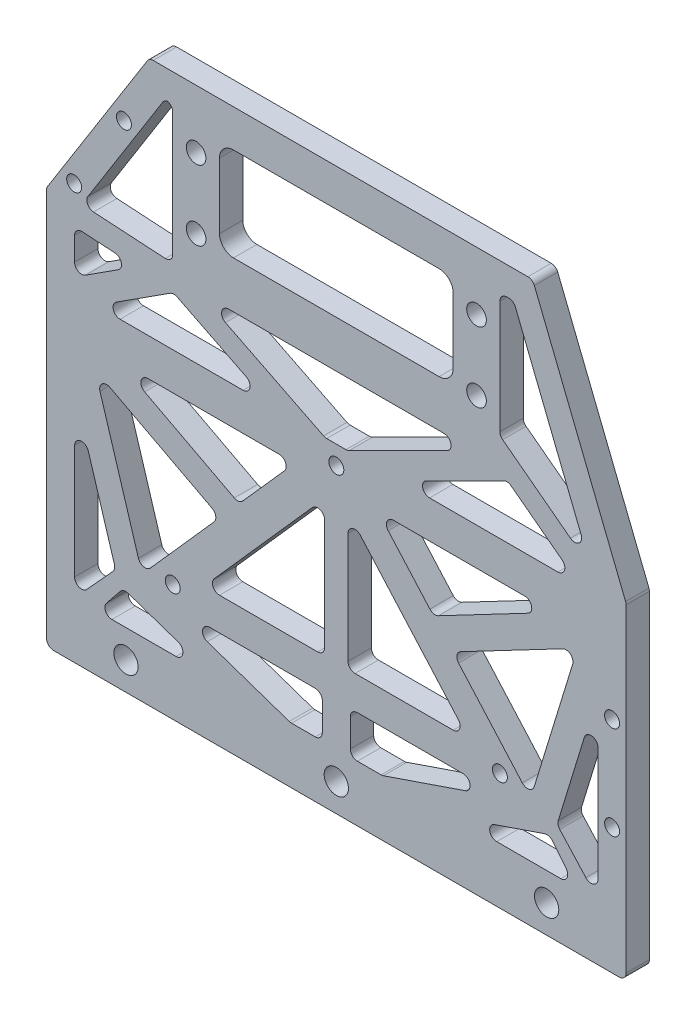
SolidWorks part; units mm, degrees
material "Thornel Mat VMA"
ref_plane "前视基准面" through (0, 0, 0) normal (0, 0, 1) x (1, 0, 0)
ref_plane "上视基准面" through (0, 0, 0) normal (0, 1, 0) x (1, 0, 0)
ref_plane "右视基准面" through (0, 0, 0) normal (1, 0, 0) x (0, 0, -1)
sketch "草图1" plane through (0, 0, 0) normal (0, 0, 1) x (1, 0, 0)
  line L1 (-62, 60) -> (62, 60)
  line L2 (-62, 60) -> (-62, -60)
  line L3 (-62, -60) -> (62, -60)
  line L4 (62, 60) -> (62, -60)
  line L5 (-62, 60) -> (62, -60) construction
  line L6 (-62, -60) -> (62, 60) construction
  point P0 (0, 0)
  dimension "D1" = 124
  dimension "D2" = 120
extrude "凸台-拉伸1" add sketch "草图1" along normal blind 5
sketch "草图2" plane through (0, 0, 5) normal (0, 0, 1) x (1, 0, 0)
  line L0 (-35, -35) -> (35, -35) construction
  line L1 (-62, -60) -> (62, -60) construction
  circle A0 centre (-35, -35) radius 1.6
  circle A1 centre (35, -35) radius 1.6
  point P2 (0, -35)
  dimension "D3" = 3.2
  dimension "D1" = 70
  dimension "D2" = 25
extrude "切除-拉伸1" cut sketch "草图2" against normal through all
sketch "草图3" plane through (0, 0, 5) normal (0, 0, 1) x (1, 0, 0)
  circle A0 centre (0, 4.5) radius 1.6
  circle A1 centre (35, -35) radius 1.6 construction
  dimension "D1" = 3.2
  dimension "D2" = 39.5
extrude "切除-拉伸2" cut sketch "草图3" against normal through all
sketch "草图4" plane through (0, 0, 5) normal (0, 0, 1) x (1, 0, 0)
  line L1 (-30, 47.5) -> (30, 47.5) construction
  line L2 (-30, 47.5) -> (-30, 32.5) construction
  line L3 (-30, 32.5) -> (30, 32.5) construction
  line L4 (30, 47.5) -> (30, 32.5) construction
  line L5 (-30, 47.5) -> (30, 32.5) construction
  line L6 (-30, 32.5) -> (30, 47.5) construction
  circle A0 centre (-30, 47.5) radius 2.1
  circle A1 centre (30, 32.5) radius 2.1
  circle A2 centre (30, 47.5) radius 2.1
  circle A3 centre (-30, 32.5) radius 2.1
  point P0 (0, 40)
  dimension "D4" = 4.2
  dimension "D1" = 40
  dimension "D2" = 15
  dimension "D3" = 60
extrude "切除-拉伸3" cut sketch "草图4" against normal through all
chamfer "倒角1" distance 22 distance2 35 1 edges at (-62, 60, 2.5) first distance on face at (0, 60, 2.5)
chamfer "倒角2" distance 50 distance2 20 1 edges at (62, 60, 2.5) first distance on face at (62, 0, 2.5)
sketch "草图7" plane through (0, 0, 5) normal (0, 0, 1) x (1, 0, 0)
  line L0 (-45, -54) -> (45, -54) construction
  line L1 (-62, -60) -> (62, -60) construction
  circle A0 centre (-45, -54) radius 2.6
  circle A1 centre (0, -54) radius 2.6
  circle A2 centre (45, -54) radius 2.6
  point P4 (0, -54)
  dimension "D3" = 5.2
  dimension "D1" = 6
  dimension "D2" = 90
extrude "切除-拉伸4" cut sketch "草图7" against normal through all
sketch "草图8" plane through (0, 0, 0) normal (0, 0, -1) x (-1, 0, 0)
  circle A0 centre (-59, -33) radius 1.6
  circle A1 centre (-59, -13) radius 1.6
  circle A2 centre (45.4427, 45.7039) radius 1.6
  circle A3 centre (56.0861, 28.7712) radius 1.6
  circle A4 centre (30, 47.5) radius 2.1 construction
  dimension "D1" = 3.2
  dimension "D2" = 45.4427
  dimension "D3" = 56.0861
  dimension "D4" = 59
  dimension "D5" = 28.7712
  dimension "D6" = 45.7039
  dimension "D7" = 13
  dimension "D8" = 33
extrude "切除-拉伸5" cut sketch "草图8" against normal through all
sketch "草图9" plane through (0, 0, 5) normal (0, 0, 1) x (1, 0, 0)
  line L6 (0, 4.5) -> (-35, -35)
  line L7 (25, 52) -> (-25, 52)
  line L8 (25, 52) -> (25, 32)
  line L9 (25, 32) -> (-25, 32)
  line L10 (-25, 52) -> (-25, 32)
  line L11 (25, 52) -> (-25, 32) construction
  line L12 (56, -54) -> (56, 8.8445)
  line L13 (56, 8.8445) -> (37.9378, 54)
  line L14 (37.9378, 54) -> (-36.6846, 54)
  line L15 (-36.6846, 54) -> (-56, 23.2709)
  line L16 (-56, 23.2709) -> (-56, -54)
  line L17 (-56, -54) -> (56, -54)
  line L18 (56, -54) -> (56, 8.8445)
  line L19 (56, 8.8445) -> (37.9378, 54)
  line L20 (37.9378, 54) -> (-36.6846, 54)
  line L21 (-36.6846, 54) -> (-56, 23.2709)
  line L22 (-56, 23.2709) -> (-56, -54)
  line L23 (-56, -54) -> (56, -54)
  line L24 (25, 32) -> (-25, 52) construction
  line L25 (-35, -35) -> (35, -35)
  line L26 (35, -35) -> (0, 4.5)
  line L27 (43.8887, -39) -> (1.8, 8.5)
  line L28 (-1.8, 8.5) -> (-43.8887, -39)
  line L29 (-43.8887, -39) -> (43.8887, -39)
  line L30 (28.3335, -32) -> (0, -0.0236)
  line L31 (0, -0.0236) -> (-28.3335, -32)
  line L32 (-28.3335, -32) -> (28.3335, -32)
  line L33 (56, 4.5) -> (-56, 4.5)
  line L34 (56, 8.5) -> (-56, 8.5)
  line L35 (56, 0.5) -> (-56, 0.5)
  line L36 (43.8887, -39) -> (56, 0.5)
  line L37 (43.8887, -39) -> (56, -54)
  line L38 (-56, 0.5) -> (-43.8887, -39)
  line L39 (-56, -54) -> (-43.8887, -39)
  line L40 (-58.8682, -0.3794) -> (-47.2241, -38.3555)
  line L41 (47.2241, -38.3555) -> (56, -48)
  line L42 (-47.2241, -38.3555) -> (-56, -48)
  line L43 (47.2241, -38.3555) -> (58.8682, -0.3794)
  line L44 (-53.1318, 1.3794) -> (-40.5532, -39.6445)
  line L45 (36.118, 19.7639) -> (39.1448, 21.2773)
  line L46 (-52.8621, 0.5) -> (-22.8444, -15.25)
  line L47 (40.5532, -39.6445) -> (53.1318, 1.3794)
  line L48 (35, 22) -> (-35, 22)
  line L49 (-35, 62) -> (-35, 22)
  line L50 (35, 62) -> (-35, 62)
  line L51 (35, 62) -> (35, 22)
  line L52 (25, 32) -> (56, 8.5)
  line L53 (-35, 22) -> (-56, 23.2709)
  line L54 (-35, 22) -> (-56, 8.5)
  line L55 (-27.2138, 24.0334) -> (-54.6481, 6.3971)
  line L56 (-27.2138, 24.0334) -> (-55.849, 25.7663)
  line L57 (-42.7862, 19.9666) -> (-57.3519, 10.6029)
  line L58 (-42.7862, 19.9666) -> (-56.151, 20.7755)
  line L59 (35, 22) -> (0, 4.5)
  line L60 (-35, 22) -> (0, 4.5)
  line L61 (23.4897, 30.0077) -> (54.4897, 6.5077)
  line L62 (33.882, 24.2361) -> (0, 7.2951)
  line L63 (-33.882, 24.2361) -> (0, 7.2951)
  line L64 (26.5103, 33.9923) -> (57.5103, 10.4923)
  line L65 (36.118, 19.7639) -> (0, 1.7049)
  line L66 (-36.118, 19.7639) -> (0, 1.7049)
  line L67 (0, -0.0236) -> (0, -32)
  line L68 (-2.5, -0.0236) -> (-2.5, -32)
  line L69 (2.5, -0.0236) -> (2.5, -32)
  line L70 (43.8887, -39) -> (0, -54)
  line L71 (0, -54) -> (-43.8887, -39)
  line L72 (43.0801, -36.6344) -> (0, -51.358)
  line L73 (0, -51.358) -> (-43.0801, -36.6344)
  line L74 (52.8621, 0.5) -> (22.8444, -15.25)
  line L75 (51.4683, 3.1565) -> (21.4505, -12.5935)
  line L76 (-56, -48) -> (56, -48)
  line L77 (-54.256, -2.1565) -> (-24.2382, -17.9065)
  line L78 (54.256, -2.1565) -> (24.2382, -17.9065)
  line L79 (-53.6659, -55.8846) -> (-40.5532, -39.6445) construction
  line L80 (40.5532, -39.6445) -> (53.6659, -55.8846) construction
  line L81 (-51.4683, 3.1565) -> (-21.4505, -12.5935)
  line L82 (21.4505, -12.5935) -> (20.7951, -12.9373)
  line L83 (-21.4505, -12.5935) -> (-20.7951, -12.9373)
  line L84 (43.8887, -39) -> (0, 10.5315) construction
  line L85 (0, 10.5315) -> (-43.8887, -39) construction
  line L86 (44.6972, -41.3656) -> (0, -56.642)
  line L87 (0, -56.642) -> (-44.6972, -41.3656)
  line L88 (-44.6972, -41.3656) -> (-45.5605, -41.0706)
  line L89 (44.6972, -41.3656) -> (45.5605, -41.0706)
  line L90 (0, -48) -> (0, -39)
  line L91 (3, -48) -> (3, -39)
  line L92 (-3, -48) -> (-3, -39)
  line L99 (-58.3341, -52.1154) -> (-47.2241, -38.3555) construction
  line L100 (47.2241, -38.3555) -> (58.3341, -52.1154) construction
  point P0 (0, 42)
  dimension "D2" = 42
  dimension "D3" = 20
  dimension "D4" = 50
  dimension "D1" = 6
  dimension "D5" = 4
  dimension "D6" = 3
  dimension "D7" = 4
  dimension "D8" = 4
  dimension "D9" = 3
  dimension "D10" = 3
  dimension "D11" = 10
  dimension "D12" = 2.5
  dimension "D13" = 2.5
  dimension "D14" = 2.5
  dimension "D15" = 2.5
  dimension "D16" = 2.5
  dimension "D17" = 2.5
  dimension "D18" = 2.5
  dimension "D19" = 3
  dimension "D20" = 6
  dimension "D21" = 3
  dimension "D22" = 2.5
  dimension "D23" = 3
  dimension "D24" = 3
extrude "切除-拉伸6" cut sketch "草图9" against normal blind 10 contours L51 L64 L19 L20 | L7 L10 L9 L8 | L56 L49 L20 L21 | L57 L58 L22 | L48 L63 L34 L28 L27 L62 | L45 L65 L34 L61 | L66 L55 L34 | L35 L44 L28 | L27 L47 L35 | L30 L69 L32 | L68 L31 L32 | L22 L76 L40 | L81 L83 L28 L35 | L82 L75 L35 L27 | L76 L92 L29 L73 | L91 L76 L72 L29 | L89 L86 L76 L37 | L87 L88 L39 L76 | L76 L18 L43 region at (-25.363, -3.9791, 5) region at (25.363, -3.9791, 5) region at (34.0343, 12.3435, 5) region at (-33.2707, 12.0425, 5) region at (0, 17.1592, 5) region at (0, 42, 5) region at (53.0747, -32.0298, 5) region at (-51.5954, 17.4017, 5) region at (-53.0747, -32.0298, 5) region at (-41.5375, 35.483, 5) region at (-39.3584, -19.1564, 5) region at (39.3584, -19.1564, 5) region at (40.6672, -45.6902, 5) region at (41.6524, 33.1508, 5) region at (-40.6672, -45.6902, 5) region at (14.4412, -42.5121, 5) region at (-14.4412, -42.5121, 5) region at (11.1112, -22.2817, 5) region at (-11.1112, -22.2817, 5)
fillet "圆角2" radius 1.5 65 edges at (-56, -48, 2.5) (-56, -9.7338, 2.5) (-47.2241, -38.3555, 2.5) (3, -39, 2.5) (36.1585, -39, 2.5) (9.8253, -48, 2.5) (3, -48, 2.5) (20.7951, -12.9373, 2.5) (8.8887, 0.5, 2.5) (46.4052, 0.5, 2.5) (-56, 11.472, 2.5) (-56, 20.7663, 2.5) (-42.7862, 19.9666, 2.5) (2.4098, 8.5, 2.5) (-2.4098, 8.5, 2.5) (-29.4098, 22, 2.5) (29.4098, 22, 2.5) (-13.5902, 8.5, 2.5) (-51.3769, 8.5, 2.5) (-34.8452, 19.1275, 2.5) (56, -9.7338, 2.5) (56, -48, 2.5) (47.2241, -38.3555, 2.5) (37.9378, 54, 2.5) (54.3968, 12.8525, 2.5) (35, 27.5565, 2.5) (35, 54, 2.5) (-40, 60, 2.5) (-62, 25, 2.5) (-62, -60, 2.5) (62, -60, 2.5) (62, 10, 2.5) (42, 60, 2.5) (-51.1555, -48, 2.5) (-45.5605, -41.0706, 2.5) (-25.2857, -48, 2.5) (24.8936, -17.5627, 2.5) (51.6242, -3.5374, 2.5) (41.5575, -36.3691, 2.5) (-24.8936, -17.5627, 2.5) (-41.5575, -36.3691, 2.5) (-51.6242, -3.5374, 2.5) (36.6512, 20.0305, 2.5) (51.8616, 8.5, 2.5) (13.5902, 8.5, 2.5) (-54.4834, 25.6837, 2.5) (-36.6846, 54, 2.5) (-35, 54, 2.5) (-35, 24.5046, 2.5) (-36.1585, -39, 2.5) (-3, -39, 2.5) (-3, -48, 2.5) (-9.8253, -48, 2.5) (45.5605, -41.0706, 2.5) (51.1555, -48, 2.5) (25.2857, -48, 2.5) (2.5, -32, 2.5) (2.5, -2.845, 2.5) (28.3335, -32, 2.5) (-2.5, -32, 2.5) (-28.3335, -32, 2.5) (-2.5, -2.845, 2.5) (-8.8887, 0.5, 2.5) (-20.7951, -12.9373, 2.5) (-46.4052, 0.5, 2.5)
fillet "圆角3" radius 3 4 edges at (25, 32, 2.5) (-25, 52, 2.5) (25, 52, 2.5) (-25, 32, 2.5)
